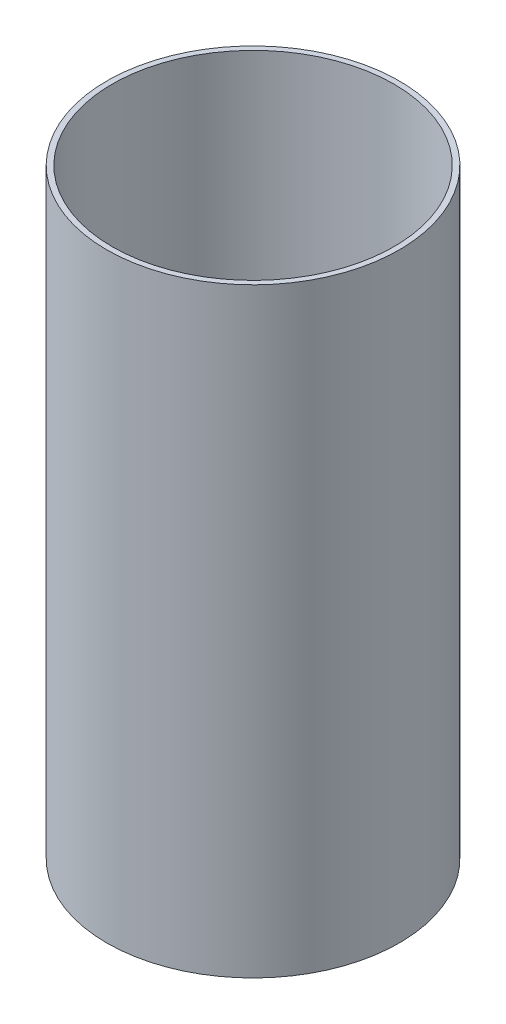
SolidWorks part; units mm, degrees
ref_plane "Front Plane" through (0, 0, 0) normal (0, 0, 1) x (1, 0, 0)
ref_plane "Top Plane" through (0, 0, 0) normal (0, 1, 0) x (1, 0, 0)
ref_plane "Right Plane" through (0, 0, 0) normal (1, 0, 0) x (0, 0, -1)
sketch "Sketch1" plane through (0, 0, 0) normal (0, 1, 0) x (1, 0, 0)
  circle A0 centre (0, 0) radius 49.5173
  circle A1 centre (0, 0) radius 47.6885
  dimension "D1" = 99.0346
  dimension "D2" = 95.377
extrude "Boss-Extrude1" add sketch "Sketch1" along normal blind 203.2
equation "\"Coupler_OD\" = 3.899in"
equation "\"Coupler_ID\" = 3.755in"
equation "\"Mid_Coupler_Length\" = 8in"
equation "\"D1@Sketch1\"=\"Coupler_OD\""
equation "\"D2@Sketch1\"=\"Coupler_ID\""
equation "\"D1@Boss-Extrude1\"=\"Mid_Coupler_Length\""
